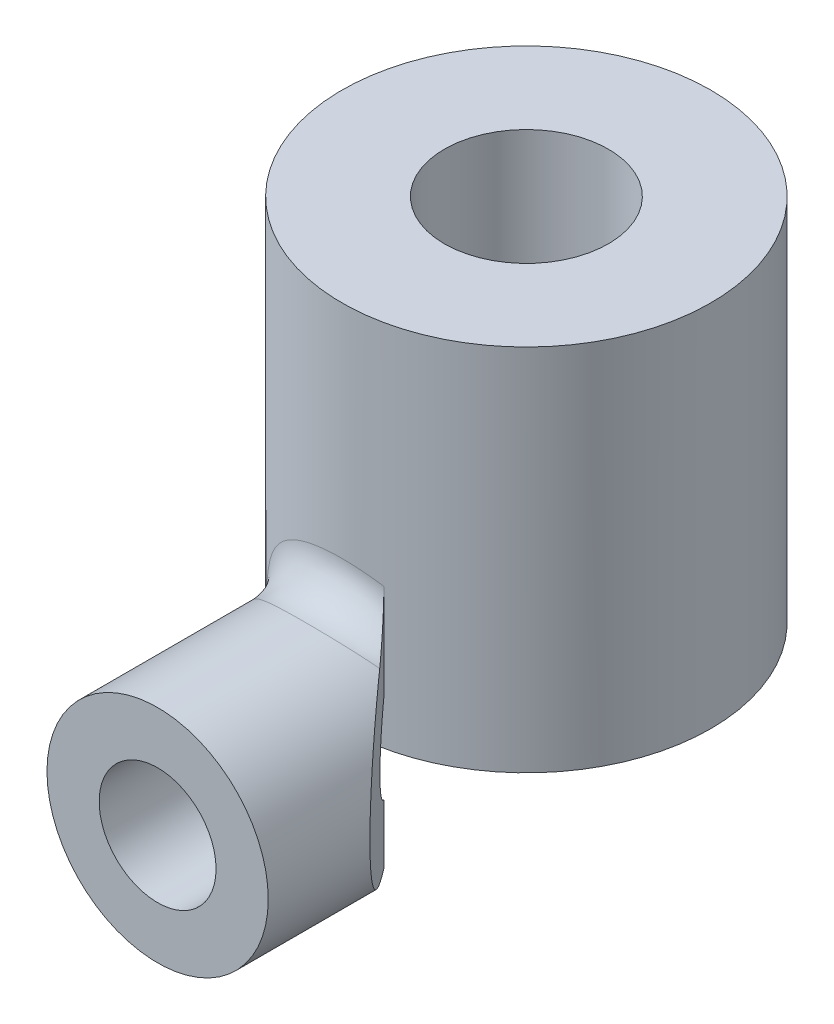
SolidWorks part; units mm, degrees
material "PE Low/Medium Density"
ref_plane "Front Plane" through (0, 0, 0) normal (0, 0, 1) x (1, 0, 0)
ref_plane "Top Plane" through (0, 0, 0) normal (0, 1, 0) x (1, 0, 0)
ref_plane "Right Plane" through (0, 0, 0) normal (1, 0, 0) x (0, 0, -1)
sketch "Sketch6" plane through (0, 0, 0) normal (0, 1, 0) x (1, 0, 0)
  circle A0 centre (0, 0) radius 5.65
  circle A1 centre (0, 0) radius 12.7
  dimension "D1" = 11.3
  dimension "D2" = 25.4
extrude "Boss-Extrude4" add sketch "Sketch6" along normal blind 25.4
sketch "Sketch8" plane through (0, 0, 0) normal (0, 0, 1) x (1, 0, 0)
  circle A0 centre (0, 0) radius 7.62
  circle A1 centre (0, 0) radius 4.0259
  dimension "D1" = 15.24
  dimension "D2" = 8.0518
extrude "Boss-Extrude6" add sketch "Sketch8" against normal up to surface (15.24 mm away) from offset 25.4 up to face at (0, 25.4, 12.7)
fillet "Fillet1" radius 2.54 1 edges at (-0.2736, 7.6151, 12.6971)
sketch "Sketch9" plane through (0, 25.4, 0) normal (0, 1, 0) x (1, 0, 0)
  line L1 (0, 2.54) -> (0, -20.32) construction
  line L5 (0, 20.32) -> (0, 12.7)
  line L7 (0, 2.54) -> (14.2699, -14.4662) construction
  line L8 (2.6127, -12.4283) -> (7.895, -18.7235)
  line L9 (-5.8373, -2.358) -> (8.4327, -19.3643) construction
  circle A2 centre (0, 0) radius 12.7 construction
  arc A4 (0, 20.32) -> (7.895, -18.7235) centre (0, 0) cw
  arc A5 (2.6127, -12.4283) -> (0, 12.7) centre (0, 0) ccw
  dimension "D4" = 2.54
  dimension "D5" = 40
  dimension "D1" = 7.62
  dimension "D6" = 7.62
extrude "Cut-Extrude1" cut sketch "Sketch9" against normal through all both and the other way through all contours L5 A5 L8 A4
